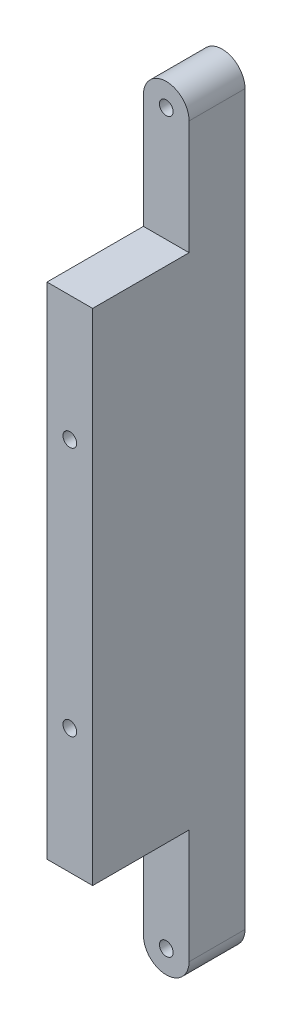
SolidWorks part; units mm, degrees
ref_plane "前视基准面" through (0, 0, 0) normal (0, 0, 1) x (1, 0, 0)
ref_plane "上视基准面" through (0, 0, 0) normal (0, 1, 0) x (1, 0, 0)
ref_plane "右视基准面" through (0, 0, 0) normal (1, 0, 0) x (0, 0, -1)
other "Configuration Table"
sketch "草图1" plane through (0, 0, 0) normal (0, 0, 1) x (1, 0, 0)
  circle A0 centre (0, 0) radius 2
  circle A1 centre (0, 0) radius 0.6
  dimension "D1" = 4
  dimension "D2" = 1.2
extrude "凸台-拉伸1" add sketch "草图1" along normal blind 20 contours A0 | A1
sketch "草图4" plane through (0, 0, 0) normal (0, 1, 0) x (1, 0, 0)
  line L0 (2, 0) -> (-2, 0) construction
  line L1 (-2, 0) -> (2, 0)
  line L2 (-2, 0) -> (-2, -20)
  line L3 (-2, -20) -> (2, -20)
  line L4 (2, 0) -> (2, -20)
  line L5 (-2, -20) -> (2, -20) construction
  line L6 (2, -20) -> (2, 0) construction
  point P10 (-1.2394, 0)
extrude "凸台-拉伸2" add sketch "草图4" along normal blind 10
sketch "草图3" plane through (0, 10, 0) normal (0, 1, 0) x (1, 0, 0)
  line L0 (-2, -10) -> (2, -10) construction
  line L1 (-2, -4.9) -> (2, -4.9)
  line L2 (-2, -4.9) -> (-2, -15.1)
  line L3 (-2, -15.1) -> (2, -15.1)
  line L4 (2, -4.9) -> (2, -15.1)
  line L7 (-2, 0) -> (-2, -20) construction
  line L8 (2, -20) -> (2, 0) construction
  point P6 (0.1529, -10)
  point P8 (0.7603, -10)
  point P10 (0, 0)
  point P12 (0, 0)
  dimension "D1" = 10.2
extrude "切除-拉伸1" cut sketch "草图3" against normal through all
extrude "凸台-拉伸3" add sketch "草图4<2>" along normal blind 3 from surface starting at face at (0, 10, 2.45)
sketch "草图4<2>" plane through (0, 0, 0) normal (0, 1, 0) x (1, 0, 0) same geometry as "草图4"
extrude "切除-拉伸3" cut sketch "草图1<4>" along normal through all contours A1
sketch "草图1<4>" plane through (0, 0, 0) normal (0, 0, 1) x (1, 0, 0) same geometry as "草图1"
sketch "草图5" plane through (0, 0, 0) normal (0, 0, -1) x (-1, 0, 0)
  line L1 (-2, 13) -> (-2, 0) construction
  line L2 (-2, 13) -> (2, 13)
  line L3 (-2, 13) -> (-2, 31.9)
  line L4 (-2, 31.9) -> (2, 31.9)
  line L5 (2, 13) -> (2, 31.9)
  line L6 (2, 13) -> (2, 0) construction
  line L7 (2, 13) -> (-2, 13) construction
  point P11 (0.7938, 7.3999)
  point P13 (0, 0)
  point P14 (1.25, 7.856)
  dimension "D1" = 31.9
extrude "凸台-拉伸4" add sketch "草图5" against normal up to surface (20 mm away) up to face at (0, 6, 20)
mirror "镜向1" about plane through (2, 31.9, 39.3186) normal (0, 1, 0) of bodies 223
sketch "草图6" plane through (-2, 0, 0) normal (-1, 0, 0) x (0, 0, 1)
  line L0 (15.1, -2) -> (20, -2) construction
  line L1 (20, -2) -> (13.35, -2)
  line L2 (20, -2) -> (20, 65.8)
  line L3 (20, 65.8) -> (13.35, 65.8)
  line L4 (13.35, -2) -> (13.35, 65.8)
  line L5 (20, -2) -> (20, 0) construction
  line L6 (20, 65.8) -> (15.1, 65.8) construction
  point P8 (20, 64.8022)
  dimension "D1" = 6.65
extrude "切除-拉伸4" cut sketch "草图6" against normal through all
sketch "草图7" plane through (0, 0, 13.35) normal (0, 0, 1) x (1, 0, 0)
  line L0 (0, 53.8) -> (0, 42.85) construction
  line L1 (2, 53.8) -> (-2, 53.8) construction
  line L2 (0, 42.85) -> (0, 31.9) construction
  line L3 (0, 31.9) -> (0, 20.95) construction
  line L4 (0, 20.95) -> (0, 10) construction
  line L5 (-2, 10) -> (2, 10) construction
  circle A0 centre (0, 42.85) radius 0.6
  circle A1 centre (0, 20.95) radius 0.6
  dimension "D1" = 1.2
extrude "切除-拉伸5" cut sketch "草图7" against normal blind 3
